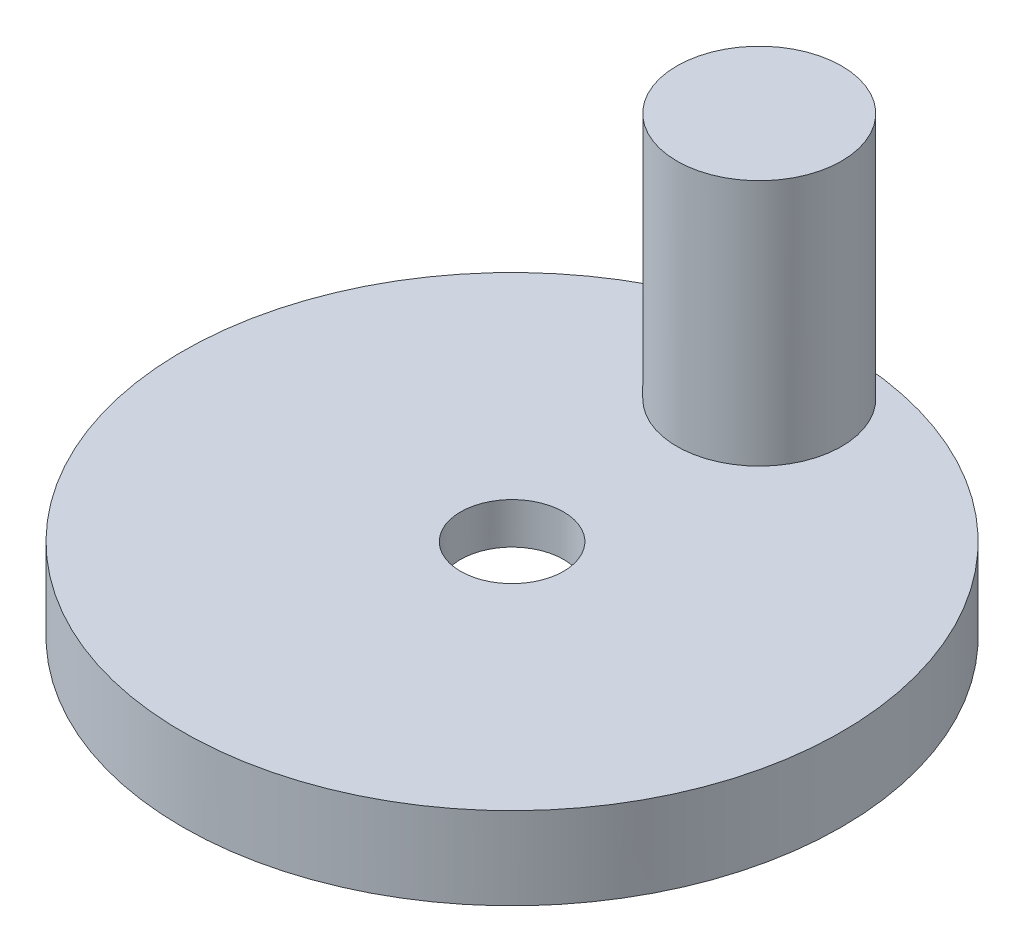
SolidWorks part; units mm, degrees
ref_plane "前视基准面" through (0, 0, 0) normal (0, 0, 1) x (1, 0, 0)
ref_plane "上视基准面" through (0, 0, 0) normal (0, 1, 0) x (1, 0, 0)
ref_plane "右视基准面" through (0, 0, 0) normal (1, 0, 0) x (0, 0, -1)
other "Configuration Table"
sketch "草图1" plane through (0, 0, 0) normal (0, 1, 0) x (1, 0, 0)
  circle A0 centre (0, 0) radius 1.25
  circle A1 centre (0, 0) radius 8
  dimension "D1" = 2.5
  dimension "D2" = 16
extrude "凸台-拉伸1" add sketch "草图1" along normal blind 2
sketch "草图2" plane through (0, 0, 0) normal (0, -1, 0) x (1, 0, 0)
  circle A0 centre (0, 0) radius 4
  dimension "D1" = 8
extrude "切除-拉伸1" cut sketch "草图2" against normal blind 1
sketch "草图3" plane through (0, 2, 0) normal (0, 1, 0) x (1, 0, 0)
  line L0 (0, 6) -> (0, 0) construction
  circle A0 centre (0, 6) radius 2
  circle A1 centre (0, 0) radius 8 construction
  dimension "D1" = 4
extrude "凸台-拉伸2" add sketch "草图3" along normal blind 6
